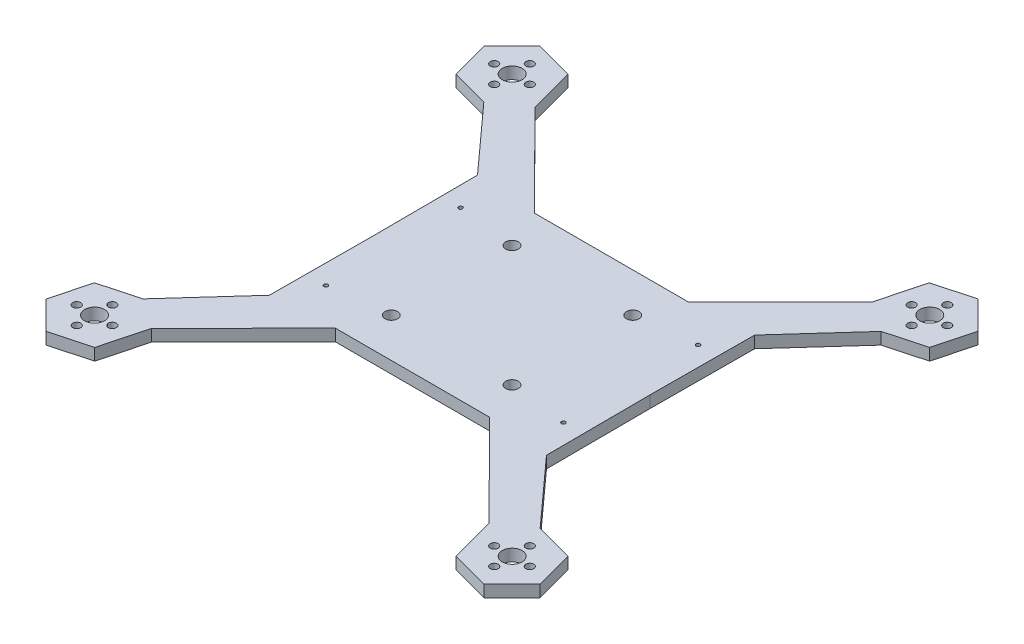
SolidWorks part; units mm, degrees
material "T700G"
ref_plane "Front Plane" through (0, 0, 0) normal (0, 0, 1) x (1, 0, 0)
ref_plane "Top Plane" through (0, 0, 0) normal (0, 1, 0) x (1, 0, 0)
ref_plane "Right Plane" through (0, 0, 0) normal (1, 0, 0) x (0, 0, -1)
sketch "Sketch1" plane through (0, 0, 0) normal (0, 1, 0) x (1, 0, 0)
  line L5 (-35, -35) -> (42.6186, 42.6186) construction
  line L6 (-35, 35) -> (35, -35) construction
  line L9 (0, 0) -> (42.4264, 42.4264) construction
  line L10 (52.7307, 48.2307) -> (52.7307, 57.2307) construction
  line L11 (30, 17) -> (30, 0) construction
  line L12 (0, 0) -> (0, 23.6863) construction
  line L28 (0, 0) -> (-174.2372, 0) construction
  line L41 (31.9599, 25.1581) -> (-25.1581, 25.1581) construction
  line L70 (42.6186, 48.4021) -> (19.4638, 25.1581)
  line L72 (48.2307, 52.7307) -> (57.2307, 52.7307) construction
  line L74 (48.2307, 52.7307) -> (52.7307, 48.2307) construction
  line L75 (55.3003, 62.3949) -> (45.646, 59.7881)
  line L77 (45.646, 59.7881) -> (42.6186, 48.4021)
  line L80 (50.185, 43.0729) -> (59.8153, 45.6732)
  line L83 (59.8153, 45.6732) -> (62.3849, 55.3374)
  line L85 (62.3849, 55.3374) -> (55.3003, 62.3949)
  line L87 (50.185, 43.0729) -> (35, 26.2883)
  line L88 (35, 26.2883) -> (34.873, 0)
  line L89 (34.873, -11.873) -> (34.873, 11.873) construction
  line L90 (-21.8355, 25.1581) -> (21.8355, 25.1581)
  line L94 (35, -26.2883) -> (34.873, 0)
  line L100 (48.2307, -52.7307) -> (52.7307, -48.2307) construction
  line L101 (48.2307, -52.7307) -> (57.2307, -52.7307) construction
  line L102 (52.7307, -48.2307) -> (52.7307, -57.2307) construction
  line L106 (62.3849, -55.3374) -> (55.3003, -62.3949)
  line L111 (59.8153, -45.6732) -> (62.3849, -55.3374)
  line L115 (50.185, -43.0729) -> (59.8153, -45.6732)
  line L116 (45.646, -59.7881) -> (42.6186, -48.4021)
  line L119 (55.3003, -62.3949) -> (45.646, -59.7881)
  line L127 (50.185, -43.0729) -> (35, -26.2883)
  line L128 (35, 26.2883) -> (34.873, 0)
  line L129 (35, -26.2883) -> (34.873, 0)
  line L135 (42.6186, -48.4021) -> (19.4638, -25.1581)
  line L138 (40.4517, 52.7386) -> (49.1512, 44.0725) [skipped]
  line L139 (-21.8355, -25.1581) -> (21.8355, -25.1581)
  line L140 (-48.2307, 52.7307) -> (-52.7307, 48.2307) construction
  line L141 (-48.2307, 52.7307) -> (-57.2307, 52.7307) construction
  line L142 (-52.7307, 48.2307) -> (-52.7307, 57.2307) construction
  line L143 (-62.3849, 55.3374) -> (-55.3003, 62.3949)
  line L144 (-59.8153, 45.6732) -> (-62.3849, 55.3374)
  line L145 (-50.185, 43.0729) -> (-59.8153, 45.6732)
  line L146 (-45.646, 59.7881) -> (-42.6186, 48.4021)
  line L147 (-55.3003, 62.3949) -> (-45.646, 59.7881)
  line L148 (-50.185, 43.0729) -> (-35, 26.2883)
  line L149 (-42.6186, 48.4021) -> (-19.4638, 25.1581)
  line L150 (-35, 26.2883) -> (-34.873, 0)
  line L151 (-35, -26.2883) -> (-34.873, 0)
  line L152 (-50.185, -43.0729) -> (-35, -26.2883)
  line L153 (-42.6186, -48.4021) -> (-19.4638, -25.1581)
  line L154 (-52.7307, -48.2307) -> (-52.7307, -57.2307) construction
  line L155 (-48.2307, -52.7307) -> (-57.2307, -52.7307) construction
  line L156 (-48.2307, -52.7307) -> (-52.7307, -48.2307) construction
  line L157 (-55.3003, -62.3949) -> (-45.646, -59.7881)
  line L158 (-45.646, -59.7881) -> (-42.6186, -48.4021)
  line L159 (-50.185, -43.0729) -> (-59.8153, -45.6732)
  line L160 (-59.8153, -45.6732) -> (-62.3849, -55.3374)
  line L161 (-62.3849, -55.3374) -> (-55.3003, -62.3949)
  circle A0 centre (-15.25, 15.25) radius 1.6
  circle A1 centre (15.25, 15.25) radius 1.6
  circle A2 centre (15.25, -15.25) radius 1.6
  circle A3 centre (-15.25, -15.25) radius 1.6
  circle A18 centre (30, 17) radius 0.5
  circle A19 centre (30, -17) radius 0.5
  circle A20 centre (-30, -17) radius 0.5
  circle A21 centre (-30, 17) radius 0.5
  circle A69 centre (52.7307, 52.7307) radius 8.6603 construction
  circle A70 centre (52.7307, 57.2307) radius 1
  circle A71 centre (52.7307, 48.2307) radius 1
  circle A72 centre (48.2307, 52.7307) radius 1
  circle A73 centre (57.2307, 52.7307) radius 1
  circle A124 centre (52.7307, -52.7307) radius 8.6603 construction
  circle A125 centre (57.2307, -52.7307) radius 1
  circle A126 centre (48.2307, -52.7307) radius 1
  circle A127 centre (52.7307, -48.2307) radius 1
  circle A128 centre (52.7307, -57.2307) radius 1
  circle A129 centre (-52.7307, 52.7307) radius 8.6603 construction
  circle A130 centre (-57.2307, 52.7307) radius 1
  circle A131 centre (-48.2307, 52.7307) radius 1
  circle A132 centre (-52.7307, 48.2307) radius 1
  circle A133 centre (-52.7307, 57.2307) radius 1
  circle A134 centre (-52.7307, -52.7307) radius 8.6603 construction
  circle A135 centre (-52.7307, -57.2307) radius 1
  circle A136 centre (-52.7307, -48.2307) radius 1
  circle A137 centre (-48.2307, -52.7307) radius 1
  circle A138 centre (-57.2307, -52.7307) radius 1
  point P0 (0, 0)
  point P8 (52.7307, 52.7307)
  point P9 (52.7307, 52.7307)
  point P17 (0, 0)
  point P45 (24.8566, 0)
  point P47 (30, 0)
  point P90 (0, 25.1581)
  point P95 (0, -25.1581)
  point P96 (0, 25.1581)
  point P99 (0, 25.1581)
  point P110 (0, -25.1581)
  point P118 (0, 0)
  point P126 (0, -25.1581)
  dimension "D3" = 3.2
  dimension "D16" = 1
  dimension "D1" = 70
  dimension "D2" = 4.5
  dimension "D4" = 30.5
  dimension "D6" = 4.5
  dimension "D7" = 20
  dimension "D15" = 17
  dimension "D12" = 30
  dimension "D5" = 4
  dimension "D17" = 2
extrude "Boss-Extrude1" add sketch "Sketch1" along normal blind 3 contours L144 A21 A0 A1 A2 A3 region at (0, 0, 0)
sketch "Sketch7" plane through (0, 3, 0) normal (0, 1, 0) x (1, 0, 0)
  line L0 (-57.2307, -52.7307) -> (-48.2307, -52.7307) construction
  line L1 (-52.7307, -57.2307) -> (-52.7307, -48.2307) construction
  line L2 (0, 0) -> (-75.1546, 0) construction
  line L3 (0, 0) -> (0, 55.538) construction
  circle A0 centre (-52.7307, -52.7307) radius 0.75
  circle A1 centre (-52.7307, 52.7307) radius 0.75
  circle A2 centre (52.7307, 52.7307) radius 0.75
  circle A3 centre (52.7307, -52.7307) radius 0.75
  dimension "D1" = 1.5
extrude "Boss-Extrude4" add sketch "Sketch7" along normal blind 0.05
sketch "Sketch8" plane through (0, 3, 0) normal (0, 1, 0) x (1, 0, 0)
  circle A0 centre (-52.7307, -52.7307) radius 2.5
  circle A1 centre (52.7693, -52.7307) radius 2.5
  circle A2 centre (52.7693, 52.7693) radius 2.5
  circle A3 centre (-52.7307, 52.7693) radius 2.5
  dimension "D1" = 2
  dimension "D2" = 2
extrude "Cut-Extrude7" cut sketch "Sketch8" against normal blind 10
